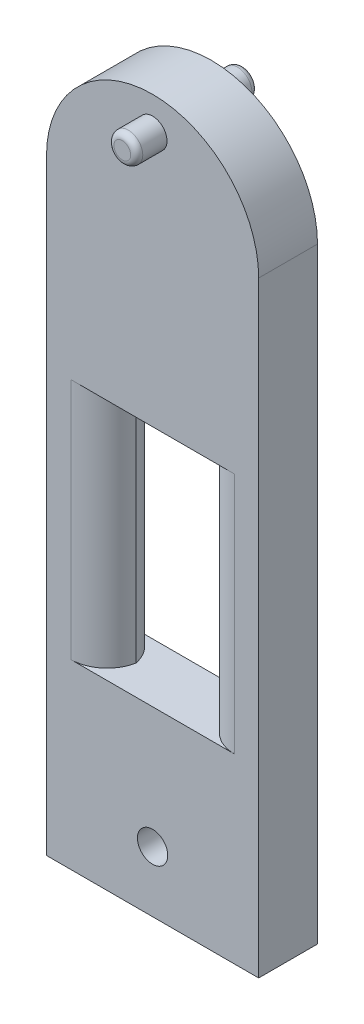
SolidWorks part; units mm, degrees
ref_plane "Front" through (0, 0, 0) normal (0, 0, 1) x (1, 0, 0)
ref_plane "Top" through (0, 0, 0) normal (0, 1, 0) x (1, 0, 0)
ref_plane "Right" through (0, 0, 0) normal (1, 0, 0) x (0, 0, -1)
sketch "Sketch1" plane through (0, 0, 0) normal (0, 0, 1) x (1, 0, 0)
  line L0 (0, -55) -> (0, 55) construction
  line L1 (-17.5, 50) -> (17.5, 50)
  line L2 (-17.5, 50) -> (-17.5, -50)
  line L3 (-17.5, -50) -> (17.5, -50)
  line L4 (17.5, 50) -> (17.5, -50)
  line L5 (-17.5, 50) -> (17.5, -50) construction
  line L6 (-17.5, -50) -> (17.5, 50) construction
  line L7 (-7.5, 20) -> (7.5, 20)
  line L8 (-7.5, 20) -> (-7.5, -20)
  line L9 (-7.5, -20) -> (7.5, -20)
  line L10 (7.5, 20) -> (7.5, -20)
  line L11 (-7.5, 20) -> (7.5, -20) construction
  line L12 (-7.5, -20) -> (7.5, 20) construction
  circle A0 centre (0, -40) radius 2.5
  arc A1 (-17.5, 50) -> (17.5, 50) centre (0, 50) cw
  point P0 (0, 0)
  point P6 (0, 0)
  point P15 (18.176, 48.868)
  dimension "D1" = 5
  dimension "D2" = 100
  dimension "D3" = 30
  dimension "D4" = 10
  dimension "D5" = 10
  dimension "D6" = 35
extrude "Boss-Extrude1" add sketch "Sketch1" along normal blind 9.7 contours A1 L2 L3 L4 A0 L7 L10 L9 L8 | A1 L1 region at (0, 57.4272, 0) region at (0, 48.9405, 0)
sketch "Sketch2" plane through (0, 0, 9.7) normal (0, 0, 1) x (1, 0, 0)
  line L0 (0, -55) -> (0, 55) construction
  circle A0 centre (0, 62) radius 2.38
  arc A1 (17.5, 50) -> (-17.5, 50) centre (0, 50) ccw construction
  dimension "D1" = 4.76
  dimension "D2" = 12
extrude "Boss-Extrude2" add sketch "Sketch2" along normal mid plane 20 from offset 5 offset against normal yes
fillet "Fillet1" radius 1 2 edges at (2.38, 62, -5.3) (2.38, 62, 14.7)
fillet "Fillet2" radius 6 4 edges at (7.5, 0, 0) (7.5, 0, 9.7) (-7.5, 0, 9.7) (-7.5, 0, 0)
